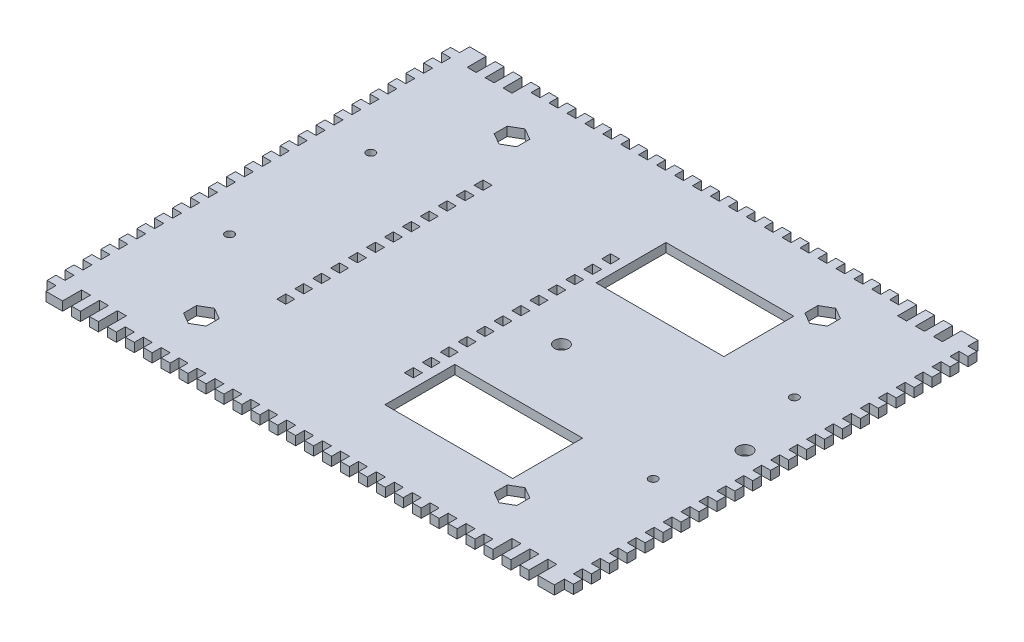
SolidWorks part; units mm, degrees
ref_plane "Front Plane" through (0, 0, 0) normal (0, 0, 1) x (1, 0, 0)
ref_plane "Top Plane" through (0, 0, 0) normal (0, 1, 0) x (1, 0, 0)
ref_plane "Right Plane" through (0, 0, 0) normal (1, 0, 0) x (0, 0, -1)
sketch "Sketch1" plane through (0, 0, 0) normal (0, 1, 0) x (1, 0, 0)
  line L1 (90, -75) -> (-90, -75)
  line L2 (90, -75) -> (90, 75)
  line L3 (90, 75) -> (-90, 75)
  line L4 (-90, -75) -> (-90, 75)
  line L5 (90, -75) -> (-90, 75) construction
  line L6 (90, 75) -> (-90, -75) construction
  point P0 (0, 0)
  dimension "D1" = 180
  dimension "D2" = 150
extrude "Boss-Extrude1" add sketch "Sketch1" along normal blind 3.175
sketch "Sketch2" plane through (0, 3.175, 0) normal (0, 1, 0) x (1, 0, 0)
  line L1 (66.1872, -39.5) -> (-33.8128, -39.5) construction
  line L2 (66.1872, -39.5) -> (66.1872, 39.5) construction
  line L3 (66.1872, 39.5) -> (-33.8128, 39.5) construction
  line L4 (-33.8128, -39.5) -> (-33.8128, 39.5) construction
  line L5 (66.1872, -39.5) -> (-33.8128, 39.5) construction
  line L6 (66.1872, 39.5) -> (-33.8128, -39.5) construction
  point P0 (16.1872, 0)
  dimension "D1" = 100
  dimension "D2" = 79
sketch "Sketch3" plane through (0, 3.175, 0) normal (0, 1, 0) x (1, 0, 0)
  line L1 (55, -55) -> (-55, -55) construction
  line L2 (55, -55) -> (55, 55) construction
  line L3 (55, 55) -> (-55, 55) construction
  line L4 (-55, -55) -> (-55, 55) construction
  line L5 (55, -55) -> (-55, 55) construction
  line L6 (55, 55) -> (-55, -55) construction
  circle A0 centre (-55, 55) radius 2.6
  circle A1 centre (55, 55) radius 2.6
  circle A2 centre (55, -55) radius 2.6
  circle A3 centre (-55, -55) radius 2.6
  point P0 (0, 0)
  dimension "D3" = 5.2
  dimension "D1" = 110
  dimension "D2" = 110
extrude "Cut-Extrude1" cut sketch "Sketch3" against normal blind 3.175
sketch "Sketch4" plane through (0, 3.175, 0) normal (0, 1, 0) x (1, 0, 0)
  circle A0 centre (0, 0) radius 50
  dimension "D1" = 100
extrude "Cut-Extrude2" cut sketch "Sketch4" against normal blind 3.175
sketch "Sketch5" plane through (0, 3.175, 0) normal (0, 1, 0) x (1, 0, 0)
  line L0 (-90, 75) -> (-90, -75) construction
  line L1 (-86.825, -1.5875) -> (-93.175, -1.5875)
  line L2 (-86.825, -1.5875) -> (-86.825, 1.5875)
  line L3 (-86.825, 1.5875) -> (-93.175, 1.5875)
  line L4 (-93.175, -1.5875) -> (-93.175, 1.5875)
  line L5 (-86.825, -1.5875) -> (-93.175, 1.5875) construction
  line L6 (-86.825, 1.5875) -> (-93.175, -1.5875) construction
  point P0 (-90, 0)
  dimension "D1" = 3.175
  dimension "D2" = 6.35
extrude "Boss-Extrude2" add sketch "Sketch5" against normal up to surface (3.175 mm away) up to face at (0, 0, 50)
pattern_linear "LPattern1" count 12 spacing 6.35 along (0, 0, 1) count 12 spacing 6.35 along (0, 0, -1) of "Boss-Extrude2"
mirror "Mirror1" about plane through (0, 0, 0) normal (1, 0, 0) of "LPattern1", "Boss-Extrude2"
sketch "Sketch6" plane through (0, 3.175, 0) normal (0, 1, 0) x (1, 0, 0)
  line L0 (-93.175, -73.4125) -> (93.175, -73.4125) construction
  line L3 (-90, -75) -> (90, -75) construction
  dimension "D1" = 1.5875
sketch "Sketch7" plane through (0, 3.175, 0) normal (0, 1, 0) x (1, 0, 0)
  line L0 (-93.175, -73.4125) -> (93.175, -73.4125) construction
  line L1 (-1.5875, -71.825) -> (1.5875, -71.825)
  line L2 (-1.5875, -71.825) -> (-1.5875, -75)
  line L3 (-1.5875, -75) -> (1.5875, -75)
  line L4 (1.5875, -71.825) -> (1.5875, -75)
  line L5 (-1.5875, -71.825) -> (1.5875, -75) construction
  line L6 (-1.5875, -75) -> (1.5875, -71.825) construction
  point P0 (0, -73.4125)
  dimension "D1" = 3.175
extrude "Cut-Extrude3" cut sketch "Sketch7" against normal blind 10
pattern_linear "LPattern2" count 14 spacing 6.35 along (1, 0, 0) count 14 spacing 6.35 along (-1, 0, 0) of "Cut-Extrude3"
mirror "Mirror2" about plane through (0, 0, 0) normal (0, 0, 1) of "LPattern2", "Cut-Extrude3"
sketch "Sketch9" plane through (0, 3.175, 0) normal (0, 1, 0) x (1, 0, 0)
  line L1 (-55, 50.3812) -> (-51, 52.6906)
  line L2 (-51, 52.6906) -> (-51, 57.3094)
  line L3 (-51, 57.3094) -> (-55, 59.6188)
  line L4 (-55, 59.6188) -> (-59, 57.3094)
  line L5 (-59, 57.3094) -> (-59, 52.6906)
  line L6 (-59, 52.6906) -> (-55, 50.3812)
  line L7 (-55, -59.6188) -> (-51, -57.3094)
  line L8 (-51, -57.3094) -> (-51, -52.6906)
  line L9 (-51, -52.6906) -> (-55, -50.3812)
  line L10 (-55, -50.3812) -> (-59, -52.6906)
  line L11 (-59, -52.6906) -> (-59, -57.3094)
  line L12 (-59, -57.3094) -> (-55, -59.6188)
  line L13 (55, 50.3812) -> (59, 52.6906)
  line L14 (59, 52.6906) -> (59, 57.3094)
  line L15 (59, 57.3094) -> (55, 59.6188)
  line L16 (55, 59.6188) -> (51, 57.3094)
  line L17 (51, 57.3094) -> (51, 52.6906)
  line L18 (51, 52.6906) -> (55, 50.3812)
  line L19 (55, -59.6188) -> (59, -57.3094)
  line L20 (59, -57.3094) -> (59, -52.6906)
  line L21 (59, -52.6906) -> (55, -50.3812)
  line L22 (55, -50.3812) -> (51, -52.6906)
  line L23 (51, -52.6906) -> (51, -57.3094)
  line L24 (51, -57.3094) -> (55, -59.6188)
  circle A0 centre (-55, 55) radius 4 construction
  circle A1 centre (-55, -55) radius 4 construction
  circle A2 centre (55, 55) radius 4 construction
  circle A3 centre (55, -55) radius 4 construction
  dimension "D1" = 8
  dimension "D2" = 8
  dimension "D3" = 8
  dimension "D4" = 8
extrude "Cut-Extrude5" cut sketch "Sketch9" against normal blind 10
sketch "Sketch11" plane through (0, 3.175, 0) normal (0, 1, 0) x (1, 0, 0)
  line L0 (-1.5875, 60) -> (-50.4125, 60)
  line L1 (-1.5875, 60) -> (1.5875, 60)
  line L3 (-1.5875, -60) -> (1.5875, -60)
  line L5 (-50.4125, 60) -> (-50.4125, -60)
  line L6 (-50.4125, -60) -> (-1.5875, -60)
  line L9 (1.5875, 60) -> (4.7625, 60)
  line L11 (1.5875, -60) -> (4.7625, -60)
  line L12 (4.7625, 60) -> (4.7625, -60)
  dimension "D1" = 3.175
  dimension "D4" = 60
extrude "Boss-Extrude3" add sketch "Sketch11" against normal up to surface (3.175 mm away) up to face at (-55, 0, 55)
sketch "Sketch10" plane through (0, 3.175, 0) normal (0, 1, 0) x (1, 0, 0)
  line L1 (-1.5875, 4.7625) -> (1.5875, 4.7625)
  line L2 (-1.5875, 4.7625) -> (-1.5875, 1.5875)
  line L3 (-1.5875, 1.5875) -> (1.5875, 1.5875)
  line L4 (1.5875, 4.7625) -> (1.5875, 1.5875)
  line L5 (-1.5875, 4.7625) -> (1.5875, 1.5875) construction
  line L6 (-1.5875, 1.5875) -> (1.5875, 4.7625) construction
  point P0 (0, 3.175)
  dimension "D1" = 3.175
  dimension "D2" = 3.175
  dimension "D3" = 3.175
extrude "Cut-Extrude7" cut sketch "Sketch10" against normal blind 10
pattern_linear "LPattern3" count 7 spacing 6.35 along (0, 0, 1) count 7 spacing 6.35 along (0, 0, -1) skipping (0, 6) of "Cut-Extrude7"
sketch "Sketch12" plane through (0, 3.175, 0) normal (0, 1, 0) x (1, 0, 0)
  line L1 (75, -25) -> (-75, -25) construction
  line L2 (75, -25) -> (75, 25) construction
  line L3 (75, 25) -> (-75, 25) construction
  line L4 (-75, -25) -> (-75, 25) construction
  line L5 (75, -25) -> (-75, 25) construction
  line L6 (75, 25) -> (-75, -25) construction
  point P0 (0, 0)
  dimension "D1" = 150
  dimension "D2" = 50
sketch "Sketch13" plane through (0, 3.175, 0) normal (0, 1, 0) x (1, 0, 0)
  circle A0 centre (75, -25) radius 1.5
  circle A1 centre (75, 25) radius 1.5
  circle A2 centre (-75, 25) radius 1.5
  circle A3 centre (-75, -25) radius 1.5
  dimension "D1" = 3
extrude "Cut-Extrude8" cut sketch "Sketch13" against normal blind 10
sketch "Sketch14" plane through (0, 3.175, 0) normal (0, 1, 0) x (1, 0, 0)
  line L1 (-55, 46.5875) -> (-45, 46.5875)
  line L2 (-55, 46.5875) -> (-55, 43.4125)
  line L3 (-55, 43.4125) -> (-45, 43.4125)
  line L4 (-45, 46.5875) -> (-45, 43.4125)
  line L5 (-55, 46.5875) -> (-45, 43.4125) construction
  line L6 (-55, 43.4125) -> (-45, 46.5875) construction
  point P0 (-50, 45)
  dimension "D1" = 10
  dimension "D2" = 3.175
  dimension "D3" = 50
  dimension "D4" = 45
extrude "Cut-Extrude9" [suppressed] cut sketch "Sketch14" against normal blind 10
mirror "Mirror3" [suppressed] about plane through (0, 0, 0) normal (0, 0, 1)
sketch "Sketch15" plane through (0, 3.175, 0) normal (0, 1, 0) x (1, 0, 0)
  line L0 (-93.175, 68.2625) -> (-90, 68.2625) construction
  line L1 (-84.1375, 71.825) -> (-80.9625, 71.825)
  line L2 (-84.1375, 71.825) -> (-84.1375, 68.2625)
  line L3 (-84.1375, 68.2625) -> (-80.9625, 68.2625)
  line L4 (-80.9625, 71.825) -> (-80.9625, 68.2625)
extrude "Cut-Extrude10" cut sketch "Sketch15" against normal blind 10
pattern_linear "LPattern4" count 3 spacing 6.35 along (1, 0, 0) of "Cut-Extrude10"
mirror "Mirror4" about plane through (0, 0, 0) normal (1, 0, 0) of "LPattern4", "Cut-Extrude10"
mirror "Mirror5" about plane through (0, 0, 0) normal (0, 0, 1) of "Mirror4", "Cut-Extrude10", "LPattern4"
sketch "Sketch17" plane through (0, 3.175, 0) normal (0, 1, 0) x (1, 0, 0)
  line L0 (75, 25) -> (-75, 25) construction
  line L1 (4.7625, 25) -> (50, 25)
  line L2 (4.7625, 25) -> (4.7625, 49.7727)
  line L3 (4.7625, 49.7727) -> (50, 49.7727)
  line L4 (50, 25) -> (50, 49.7727)
  line L5 (4.7625, -49.7727) -> (4.7625, 49.7727) construction
extrude "Cut-Extrude11" cut sketch "Sketch17" against normal blind 10
mirror "Mirror6" about plane through (0, 0, 0) normal (0, 0, 1) of "Cut-Extrude11"
sketch "Sketch18" plane through (0, 3.175, 0) normal (0, 1, 0) x (1, 0, 0)
  line L0 (75, -25) -> (-75, -25) construction
  line L1 (50, 25) -> (4.7625, 25)
  line L2 (50, 25) -> (50, -25)
  line L3 (50, -25) -> (4.7625, -25)
  line L4 (4.7625, 25) -> (4.7625, -25)
  line L5 (4.7625, -49.7727) -> (4.7625, 49.7727) construction
extrude "Boss-Extrude4" add sketch "Sketch18" against normal up to surface (3.175 mm away) up to face at (0, 0, 0)
sketch "Sketch19" plane through (0, 3.175, 0) normal (0, 1, 0) x (1, 0, 0)
  line L0 (17.5, 0) -> (82.5, 0) construction
  line L1 (90, -23.8125) -> (90, -20.6375) construction
  circle A0 centre (17.5, 0) radius 2.5
  circle A1 centre (82.5, 0) radius 2.5
  point P4 (50, 0)
  dimension "D3" = 5
  dimension "D4" = 5
  dimension "D1" = 65
  dimension "D2" = 40
extrude "Cut-Extrude12" cut sketch "Sketch19" against normal blind 10
sketch "Sketch20" plane through (0, 3.175, 0) normal (0, 1, 0) x (1, 0, 0)
  line L0 (-1.5875, 4.7625) -> (-1.5875, 1.5875) construction
  line L1 (-46.7625, 4.7625) -> (-43.5875, 4.7625)
  line L2 (-46.7625, 4.7625) -> (-46.7625, 1.5875)
  line L3 (-46.7625, 1.5875) -> (-43.5875, 1.5875)
  line L4 (-43.5875, 4.7625) -> (-43.5875, 1.5875)
  dimension "D1" = 3.175
  dimension "D2" = 3.175
  dimension "D3" = 42
extrude "Cut-Extrude13" cut sketch "Sketch20" against normal blind 10
pattern_linear "LPattern5" count 7 spacing 6.35 along (0, 0, 1) count 7 spacing 6.35 along (0, 0, -1) skipping (0, 6) of "Cut-Extrude13"
